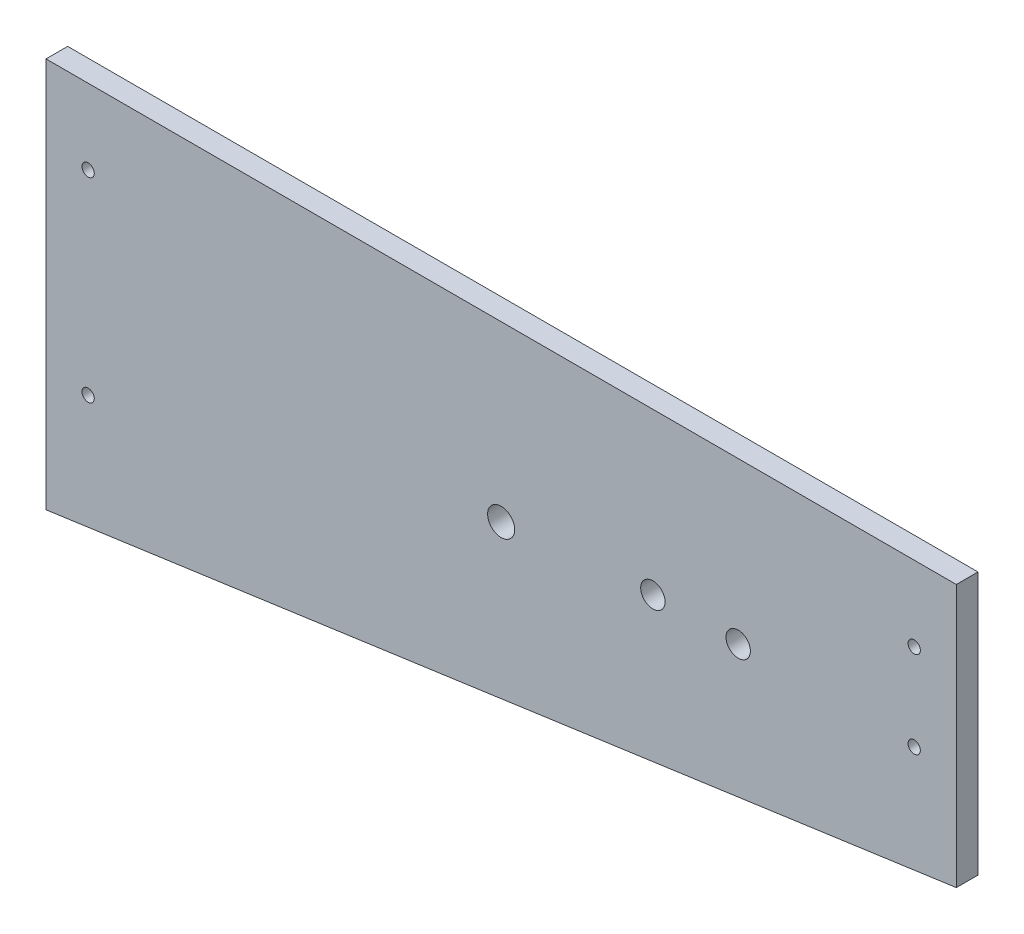
SolidWorks part; units mm, degrees
material "Acrylic (Medium-high impact)"
ref_plane "Front Plane" through (0, 0, 0) normal (0, 0, 1) x (1, 0, 0)
ref_plane "Top Plane" through (0, 0, 0) normal (0, 1, 0) x (1, 0, 0)
ref_plane "Right Plane" through (0, 0, 0) normal (1, 0, 0) x (0, 0, -1)
sketch "Sketch1" plane through (0, 0, 0) normal (0, 0, 1) x (1, 0, 0)
  line L1 (266.7, 114.4016) -> (0, 114.4016)
  line L2 (266.7, 114.4016) -> (266.7, 0)
  line L3 (266.7, 0) -> (0, 0)
  line L4 (0, 114.4016) -> (0, 0)
  line L5 (266.7, 114.4016) -> (0, 0) construction
  line L6 (266.7, 0) -> (0, 114.4016) construction
  point P0 (133.35, 57.2008)
  dimension "D1" = 114.4016
  dimension "D2" = 266.7
extrude "Boss-Extrude1" add sketch "Sketch1" along normal blind 6.35
hole_wizard "M3 Clearance Hole1" positions "Sketch2" profile "Sketch3" hole size "M3" standard "ANSI Metric" end condition through all
sketch "Sketch2" plane through (0, 0, 6.35) normal (0, 0, 1) x (1, 0, 0)
  line L0 (0, 114.4016) -> (0, 0) construction
  line L1 (266.7, 114.4016) -> (0, 114.4016) construction
  line L2 (266.7, 0) -> (266.7, 114.4016) construction
  point P0 (12.3444, 92.4052)
  point P2 (12.3444, 35.2552)
  point P4 (254.3556, 67.0052)
  point P6 (254.3556, 92.4052)
  dimension "D1" = 12.3444
  dimension "D2" = 21.9964
  dimension "D3" = 12.3444
  dimension "D4" = 57.15
  dimension "D5" = 25.4
sketch "Sketch3" plane through (12.3444, 92.4052, 6.35) normal (1, 0, 0) x (0, -1, 0)
  line L0 (0, 0) -> (0, 6.35)
  line L1 (0, 6.35) -> (1.8, 6.35)
  line L2 (1.8, 6.35) -> (1.8, 0)
  line L5 (1.8, 0) -> (0, 0)
  line L11 (0, -6.35) -> (0, 107.95) construction
  dimension "Thru Hole Dia." = 3.6
  dimension "Thru Hole Depth" = 6.35
sketch "Sketch4" plane through (0, 0, 6.35) normal (0, 0, 1) x (1, 0, 0)
  line L0 (0, 114.4016) -> (0, 0) construction
  line L1 (46.99, 95.3516) -> (50.4952, 95.3516)
  line L2 (46.99, 95.3516) -> (46.99, 19.1516)
  line L3 (46.99, 19.1516) -> (50.4952, 19.1516)
  line L4 (50.4952, 95.3516) -> (50.4952, 19.1516)
  line L5 (216.2048, 95.3516) -> (219.71, 95.3516)
  line L6 (216.2048, 95.3516) -> (216.2048, 19.1516)
  line L7 (216.2048, 19.1516) -> (219.71, 19.1516)
  line L8 (219.71, 95.3516) -> (219.71, 19.1516)
  line L9 (266.7, 0) -> (266.7, 114.4016) construction
  line L10 (266.7, 114.4016) -> (0, 114.4016) construction
  dimension "D1" = 3.5052
  dimension "D2" = 76.2
  dimension "D3" = 46.99
  dimension "D4" = 46.99
  dimension "D5" = 19.05
extrude "Cut-Extrude1" [suppressed] cut sketch "Sketch4" against normal through all
sketch "Sketch5" plane through (0, 0, 6.35) normal (0, 0, 1) x (1, 0, 0)
  line L0 (0, 0) -> (266.7, 0)
  line L1 (266.7, 0) -> (266.7, 37.4822)
  line L2 (266.7, 0) -> (266.7, 114.4016) construction
  line L3 (266.7, 37.4822) -> (0, 0)
  dimension "D1" = 8
extrude "Cut-Extrude2" cut sketch "Sketch5" against normal through all
sketch "Sketch6" plane through (0, 0, 6.35) normal (0, 0, 1) x (1, 0, 0)
  line L0 (266.7, 114.4016) -> (0, 114.4016) construction
  line L1 (0, 114.4016) -> (0, 0) construction
  circle A0 centre (133.35, 63.6016) radius 3.9687
  dimension "D1" = 7.9375
  dimension "D2" = 50.8
  dimension "D3" = 133.35
extrude "diaphragm" cut sketch "Sketch6" against normal through all
hole_wizard "1/4 Clearance Hole1" positions "Sketch7" profile "Sketch8" hole size "1/4" standard "ANSI Inch" end condition through all
sketch "Sketch7" plane through (0, 0, 6.35) normal (0, 0, 1) x (1, 0, 0)
  line L0 (0, 114.4016) -> (0, 0) construction
  line L1 (266.7, 37.4822) -> (0, 0) construction
  point P0 (177.8, 67.31)
  point P8 (202.7936, 67.31)
  dimension "D1" = 41.91
  dimension "D2" = 177.8
  dimension "D3" = 24.9936
sketch "Sketch8" plane through (177.8, 67.31, 6.35) normal (1, 0, 0) x (0, -1, 0)
  line L0 (0, 0) -> (0, 6.35)
  line L1 (0, 6.35) -> (3.5712, 6.35)
  line L2 (3.5712, 6.35) -> (3.5712, 0)
  line L5 (3.5712, 0) -> (0, 0)
  line L11 (0, -6.35) -> (0, 107.95) construction
  dimension "Thru Hole Dia." = 7.1425
  dimension "Thru Hole Depth" = 6.35
